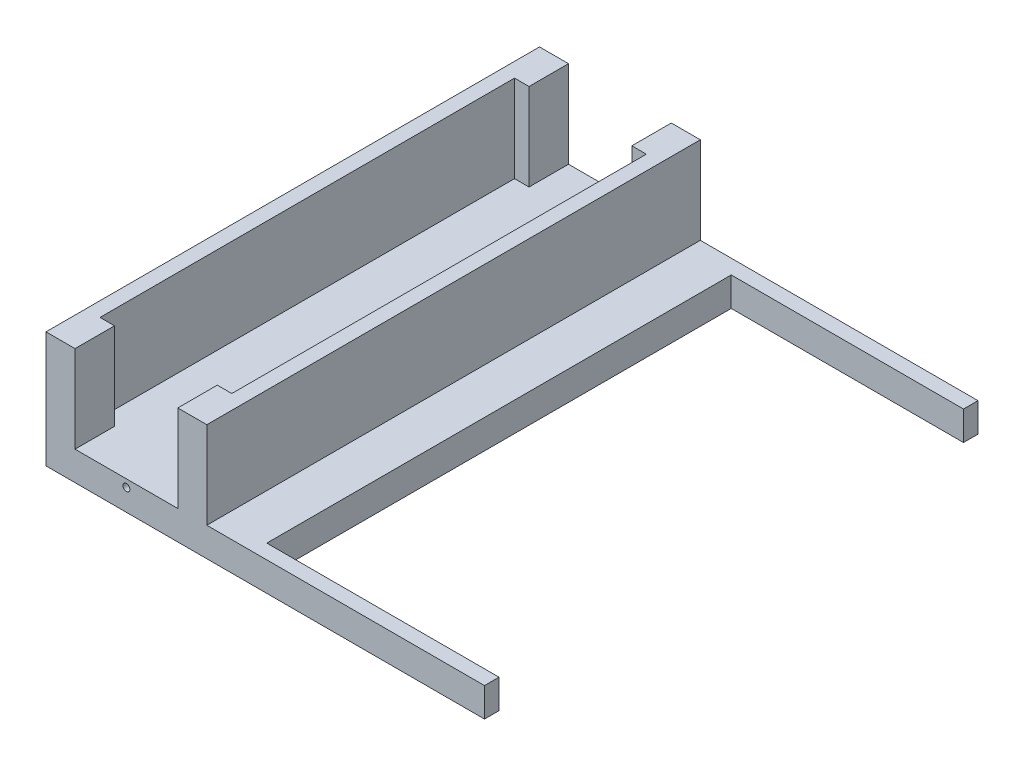
SolidWorks part; units mm, degrees
ref_plane "Front Plane" through (0, 0, 0) normal (0, 0, 1) x (1, 0, 0)
ref_plane "Top Plane" through (0, 0, 0) normal (0, 1, 0) x (1, 0, 0)
ref_plane "Right Plane" through (0, 0, 0) normal (1, 0, 0) x (0, 0, -1)
sketch "Sketch1" plane through (0, 0, 0) normal (0, 1, 0) x (1, 0, 0)
  line L0 (-55, 0) -> (55, 0) construction
  line L1 (-128.9215, -53.975) -> (128.9215, -53.975)
  line L2 (-128.9215, -53.975) -> (-128.9215, 53.975)
  line L3 (-128.9215, 53.975) -> (128.9215, 53.975)
  line L4 (128.9215, -53.975) -> (128.9215, 53.975)
  line L5 (-128.9215, -53.975) -> (128.9215, 53.975) construction
  line L6 (-128.9215, 53.975) -> (128.9215, -53.975) construction
  line L7 (-128.9215, 53.975) -> (-122.5715, 53.975)
  line L8 (-128.9215, 53.975) -> (-128.9215, 45.339)
  line L9 (-128.9215, 45.339) -> (-122.5715, 45.339)
  line L10 (-122.5715, 53.975) -> (-122.5715, 45.339)
  line L11 (-122.5715, 53.975) -> (-100.0925, 53.975)
  line L12 (-122.5715, 53.975) -> (-122.5715, 45.339)
  line L13 (-122.5715, 45.339) -> (-100.0925, 45.339)
  line L14 (-100.0925, 53.975) -> (-100.0925, 45.339)
  line L15 (-100.0925, 53.975) -> (-93.7425, 53.975)
  line L16 (-100.0925, 53.975) -> (-100.0925, 45.339)
  line L17 (-100.0925, 45.339) -> (-93.7425, 45.339)
  line L18 (-93.7425, 53.975) -> (-93.7425, 45.339)
  line L19 (-122.5715, -45.339) -> (-100.0925, -45.339)
  line L20 (-128.9215, -45.339) -> (-122.5715, -45.339)
  line L21 (-122.5715, -53.975) -> (-122.5715, -45.339)
  line L22 (-100.0925, -53.975) -> (-100.0925, -45.339)
  line L23 (-100.0925, -45.339) -> (-93.7425, -45.339)
  line L24 (-93.7425, -53.975) -> (-93.7425, -45.339)
  line L25 (-125.7465, -45.339) -> (-125.7465, 45.339)
  line L27 (-93.7425, -45.339) -> (-96.9175, -45.339)
  line L28 (-93.7425, -45.339) -> (-93.7425, 45.339)
  line L29 (-93.7425, 45.339) -> (-96.9175, 45.339)
  line L30 (-96.9175, -45.339) -> (-96.9175, 45.339)
  point P0 (0, 0)
  point P13 (-125.7465, 45.339)
  point P18 (-125.7465, -45.339)
  point P28 (102.3739, 59.436)
  point P29 (69.4921, 59.436)
  point P30 (128.9215, 59.436)
  dimension "D1" = 22.479
  dimension "D2" = 6.35
  dimension "D3" = 6.35
  dimension "D4" = 8.636
  dimension "D5" = 107.95
  dimension "D6" = 3.175
extrude "Boss-Extrude1" add sketch "Sketch1" against normal blind 6.35 contours L24 L1 L4 L3 L18 L17 L13 L9 L2 L20 L19 L23 | L1 L21 L20 L2 | L1 L24 L23 L22 | L10 L3 L2 L9 | L14 L3 L10 L13 | L18 L3 L14 L17 | L1 L22 L19 L21 | L2 L1 L4 L3 region at (-125.7465, 0, 49.657) region at (-111.332, 0, 49.657) region at (-96.9175, 0, 49.657) region at (-125.7465, 0, -49.657) region at (17.5895, 0, 0) region at (-111.332, 0, -49.657) region at (-96.9175, 0, -49.657)
extrude "Boss-Extrude2" add sketch "Sketch1<3>" along normal blind 19.05 contours L10 L3 L2 L9 | L18 L3 L14 L17 | L1 L24 L23 L22 | L1 L21 L20 L2 | L20 L25 L9 L2 | L30 L23 L28 L17 region at (-125.7465, 0, 49.657) region at (-127.334, 0, 0) region at (-96.9175, 0, 49.657) region at (-125.7465, 0, -49.657) region at (-95.33, 0, 0) region at (-96.9175, 0, -49.657)
sketch "Sketch1<3>" plane through (0, 0, 0) normal (0, 1, 0) x (1, 0, 0) same geometry as "Sketch1"
sketch "Sketch3" plane through (0, 0, 53.975) normal (0, 0, 1) x (1, 0, 0)
  line L1 (-122.5715, 0) -> (-100.0925, 0) construction
  circle A0 centre (-111.332, -1.651) radius 0.762
  dimension "D1" = 1.524
  dimension "D2" = 11.2395
  dimension "D3" = 1.651
extrude "Cut-Extrude1" cut sketch "Sketch3" against normal blind 6.35
mirror "Mirror1" about plane through (0, 0, 0) normal (0, 0, 1) of "Cut-Extrude1"
sketch "Sketch4" plane through (0, 0, 0) normal (0, 1, 0) x (1, 0, 0)
  line L1 (-83.8035, 50.8) -> (17.7965, 50.8)
  line L2 (-83.8035, 50.8) -> (-83.8035, -50.8)
  line L3 (-83.8035, -50.8) -> (17.7965, -50.8)
  line L4 (17.7965, 50.8) -> (17.7965, -50.8)
  line L5 (128.9215, -53.975) -> (128.9215, 53.975) construction
  line L6 (20.9715, 50.8) -> (122.5715, 50.8)
  line L7 (20.9715, 50.8) -> (20.9715, -50.8)
  line L8 (20.9715, -50.8) -> (122.5715, -50.8)
  line L9 (122.5715, 50.8) -> (122.5715, -50.8)
  line L11 (-93.7425, 53.975) -> (128.9215, 53.975) construction
  dimension "D1" = 101.6
  dimension "D2" = 101.6
  dimension "D3" = 101.6
  dimension "D4" = 101.6
  dimension "D5" = 6.35
  dimension "D6" = 3.175
  dimension "D7" = 3.175
  dimension "D8" = 3.175
extrude "Cut-Extrude2" cut sketch "Sketch4" against normal blind 6.35 contours L4 L1 L2 L3 region at (-33.0035, 0, 0)
sketch "Sketch5" plane through (0, 0, 0) normal (0, 1, 0) x (1, 0, 0)
  line L0 (-33.0035, 50.8) -> (-33.0035, -61.9289)
  line L2 (-83.8035, 50.8) -> (17.7965, 50.8) construction
  line L4 (-33.0035, -61.9289) -> (144.3252, -61.9289)
  line L5 (-33.0035, -61.9289) -> (-33.0035, 81.2084)
  line L6 (-33.0035, 81.2084) -> (144.3252, 81.2084)
  line L7 (144.3252, -61.9289) -> (144.3252, 81.2084)
extrude "Cut-Extrude3" cut sketch "Sketch5" against normal blind 86.614 and the other way blind 20.574 contours L4 L7 L6 L5 L0 region at (55.6609, 0, -9.6398)
